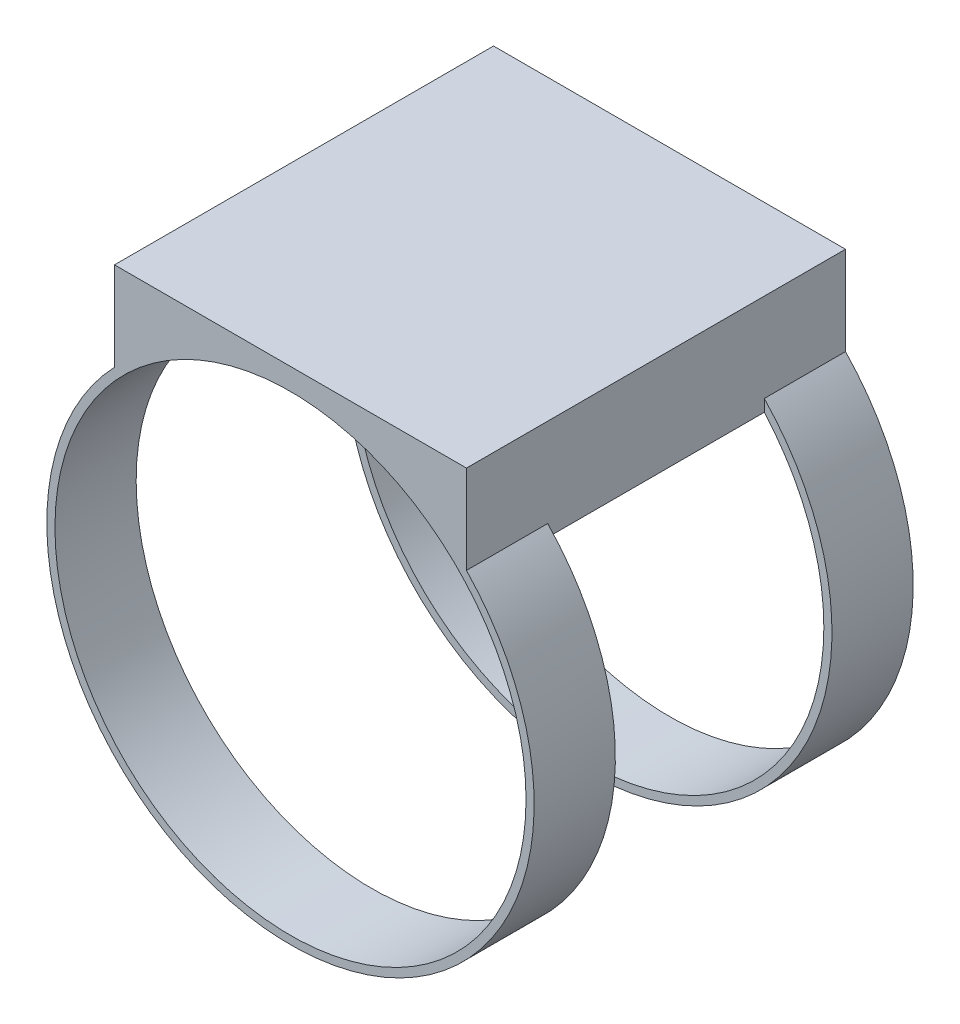
SolidWorks part; units mm, degrees
ref_plane "Front Plane" through (0, 0, 0) normal (0, 0, 1) x (1, 0, 0)
ref_plane "Top Plane" through (0, 0, 0) normal (0, 1, 0) x (1, 0, 0)
ref_plane "Right Plane" through (0, 0, 0) normal (1, 0, 0) x (0, 0, -1)
ref_plane "Plane1" through (0, 0, 0) normal (0, 0, 1) x (1, 0, 0)
sketch "Sketch1" plane through (0, 0, 0) normal (0, 0, 1) x (1, 0, 0)
  circle A0 centre (0, 0) radius 87
  circle A1 centre (0, 0) radius 90
extrude "Boss-Extrude1" add sketch "Sketch1" along normal blind 30
ref_plane "Plane2" through (0, 90, 0) normal (0, 1, 0) x (1, 0, 0)
sketch "Sketch2" plane through (0, 90, 0) normal (0, 1, 0) x (1, 0, 0)
  line L0 (-99, 0) -> (99, 0) construction
  line L1 (-65, 0) -> (65, 0)
  line L2 (-65, 0) -> (-65, -30)
  line L3 (-65, -30) -> (65, -30)
  line L4 (65, 0) -> (65, -30)
  line L5 (-90, -30) -> (90, -30) construction
extrude "Boss-Extrude2" add sketch "Sketch2" against normal up to surface and the other way blind 5 up to face at (90, 0, 30)
sketch "Sketch3" plane through (0, 0, 30) normal (0, 0, 1) x (1, 0, 0)
  line L0 (-65, 95) -> (-65, 57.8273)
  line L1 (-65, 95) -> (65, 95)
  line L2 (65, 95) -> (65, 57.8273)
  circle A1 centre (0, 0) radius 87 construction
  arc A2 (-65, 57.8273) -> (65, 57.8273) centre (0, 0) ccw
  line M2 (65, 62.2495) -> (65, 95)
  line M3 (65, 95) -> (-65, 95)
  line M4 (-65, 95) -> (-65, 62.2495)
  circle M5 centre (0, 0) radius 87
extrude "Boss-Extrude3" add sketch "Sketch3" along normal blind 40 contours L2 L0 M2 M3 M4 M5 region at (0, 93.6479, 30)
ref_plane "Plane3" through (0, 0, 70) normal (0, 0, 1) x (1, 0, 0)
mirror "Mirror2" about plane through (0, 0, 70) normal (0, 0, 1) of bodies 103
